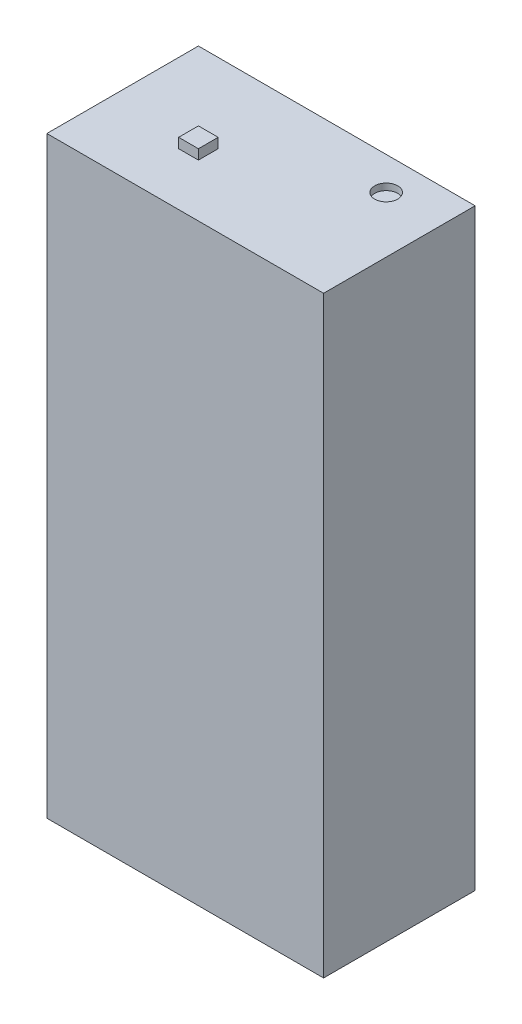
SolidWorks part; units mm, degrees
ref_plane "Front Plane" through (0, 0, 0) normal (1, 0, 0) x (0, 1, 0)
ref_plane "Top Plane" through (0, 0, 0) normal (0, 0, 1) x (0, 1, 0)
ref_plane "Right Plane" through (0, 0, 0) normal (0, 1, 0) x (-1, 0, 0)
sketch "Sketch1" plane through (0, 0, 0) normal (0, 0, 1) x (0, 1, 0)
  line L0 (-25, 12.5) -> (-25, -11.5) construction
  line L1 (-45, 21) -> (45, 21)
  line L2 (-45, 21) -> (-45, -21)
  line L3 (-45, -21) -> (45, -21)
  line L4 (45, 21) -> (45, -21)
  line L5 (-25, 12.5) -> (20, 12.5) construction
  circle A0 centre (-25, 12.5) radius 2.25
  circle A1 centre (-25, -11.5) radius 2.25
  circle A2 centre (20, -11.5) radius 2.25
  circle A3 centre (20, 12.5) radius 2.25
  point P7 (0, 21)
  point P10 (-45, 0)
  dimension "D7" = 4.5
  dimension "D1" = 90
  dimension "D2" = 42
  dimension "D3" = 2
  dimension "D4" = 2
  dimension "D5" = 20
  dimension "D6" = 8.5
  dimension "D8" = 24
  dimension "D9" = 45
extrude "Boss-Extrude1" add sketch "Sketch1" along normal blind 23 contours L4 L1 L2 L3 A3 A2 A1 A0 | A1 | A0 | A2 | A3 region at (0.0086, 0.0428, 0) region at (-12.5, -25, 0) region at (11.5, -25, 0) region at (11.5, 20, 0) region at (-12.5, 20, 0)
extrude "Cut-Extrude1" cut sketch "Sketch1<3>" along normal blind 1 contours A1 | A0 | A2 | A3 region at (-12.5, -25, 0) region at (11.5, -25, 0) region at (11.5, 20, 0) region at (-12.5, 20, 0)
sketch "Sketch1<3>" plane through (0, 0, 0) normal (0, 0, 1) x (0, 1, 0) same geometry as "Sketch1"
sketch "Sketch2" plane through (0, 45, 0) normal (0, 1, 0) x (-1, 0, 0)
  line L0 (21, 0) -> (-21, 0) construction
  line L1 (-21, 23) -> (-21, 0) construction
  line L2 (21, 23) -> (21, 0) construction
  line L3 (6, 15) -> (9, 15)
  line L4 (6, 15) -> (6, 12)
  line L5 (6, 12) -> (9, 12)
  line L6 (9, 15) -> (9, 12)
  circle A0 centre (-12.5, 5) radius 1.75
  dimension "D3" = 3.5
  dimension "D1" = 5
  dimension "D2" = 8.5
  dimension "D4" = 15
  dimension "D5" = 15
  dimension "D6" = 3
extrude "Cut-Extrude2" cut sketch "Sketch2" against normal blind 1 contours A0
extrude "Boss-Extrude2" add sketch "Sketch2<3>" along normal blind 1.5 contours L6 L3 L4 L5 region at (-7.5, 45, 13.5)
sketch "Sketch2<3>" plane through (0, 45, 0) normal (0, 1, 0) x (-1, 0, 0) same geometry as "Sketch2"
